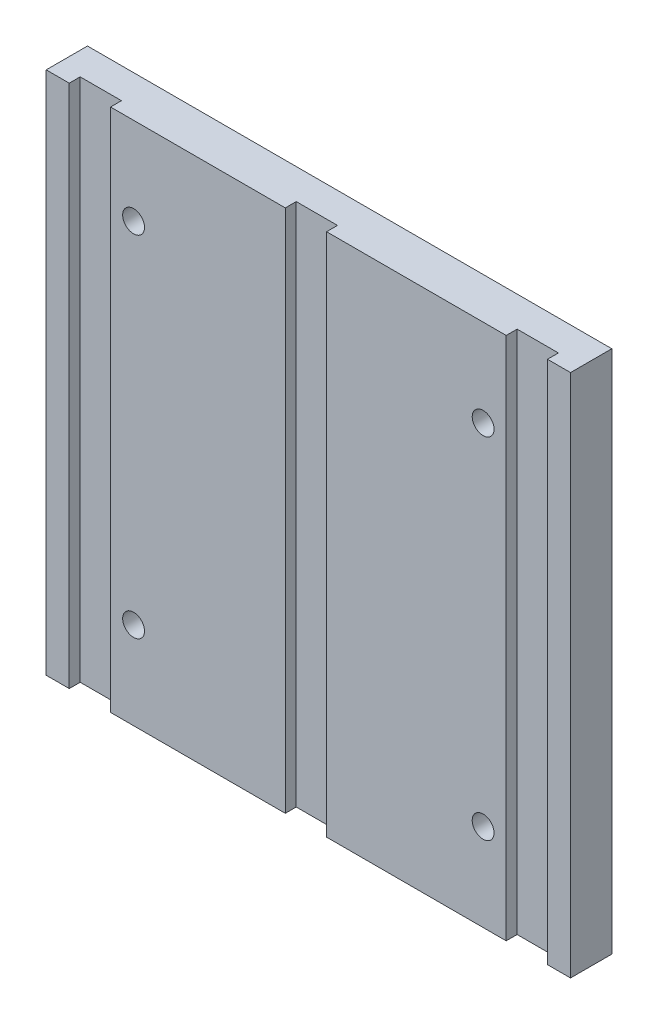
SolidWorks part; units mm, degrees
ref_plane "Front Plane" through (0, 0, 0) normal (0, 0, 1) x (1, 0, 0)
ref_plane "Top Plane" through (0, 0, 0) normal (0, 1, 0) x (1, 0, 0)
ref_plane "Right Plane" through (0, 0, 0) normal (1, 0, 0) x (0, 0, -1)
sketch "Sketch1" plane through (0, 0, 0) normal (0, 0, 1) x (1, 0, 0)
  line L1 (-76.2, 76.2) -> (76.2, 76.2)
  line L2 (-76.2, 76.2) -> (-76.2, -76.2)
  line L3 (-76.2, -76.2) -> (76.2, -76.2)
  line L4 (76.2, 76.2) -> (76.2, -76.2)
  line L5 (-76.2, 76.2) -> (76.2, -76.2) construction
  line L6 (-76.2, -76.2) -> (76.2, 76.2) construction
  circle A0 centre (-50.8, 50.8) radius 3.175
  circle A1 centre (50.8, 50.8) radius 3.175
  circle A2 centre (50.8, -50.8) radius 3.175
  circle A3 centre (-50.8, -50.8) radius 3.175
  point P0 (0, 0)
  dimension "D9" = 6.35
  dimension "D10" = 6.35
  dimension "D13" = 6.35
  dimension "D14" = 6.35
  dimension "D1" = 0
  dimension "D2" = 0
  dimension "D3" = 152.4
  dimension "D4" = 152.4
  dimension "D5" = 25.4
  dimension "D6" = 25.4
  dimension "D7" = 25.4
  dimension "D8" = 25.4
  dimension "D11" = 25.4
  dimension "D12" = 25.4
  dimension "D15" = 25.4
  dimension "D16" = 25.4
extrude "Boss-Extrude1" add sketch "Sketch1" along normal blind 12
sketch "Sketch2" plane through (0, 0, 12) normal (0, 0, 1) x (1, 0, 0)
  line L0 (-76.2, -76.2) -> (76.2, -76.2) construction
  line L1 (-69.5, 76.2) -> (-57.5, 76.2)
  line L2 (-69.5, 76.2) -> (-69.5, -76.2)
  line L3 (-69.5, -76.2) -> (-57.5, -76.2)
  line L4 (-57.5, 76.2) -> (-57.5, -76.2)
  line L5 (-69.5, 76.2) -> (-57.5, -76.2) construction
  line L6 (-69.5, -76.2) -> (-57.5, 76.2) construction
  line L7 (-6.7, 76.2) -> (5.3, 76.2)
  line L8 (-6.7, 76.2) -> (-6.7, -76.2)
  line L9 (-6.7, -76.2) -> (5.3, -76.2)
  line L10 (5.3, 76.2) -> (5.3, -76.2)
  line L11 (-6.7, 76.2) -> (5.3, -76.2) construction
  line L12 (-6.7, -76.2) -> (5.3, 76.2) construction
  line L13 (57.5, 76.2) -> (69.5, 76.2)
  line L14 (57.5, 76.2) -> (57.5, -76.2)
  line L15 (57.5, -76.2) -> (69.5, -76.2)
  line L16 (69.5, 76.2) -> (69.5, -76.2)
  line L17 (57.5, 76.2) -> (69.5, -76.2) construction
  line L18 (57.5, -76.2) -> (69.5, 76.2) construction
  line L19 (-76.2, 76.2) -> (-76.2, -76.2) construction
  line L20 (76.2, -76.2) -> (76.2, 76.2) construction
  point P0 (-63.5, 0)
  point P5 (-0.7, 0)
  point P10 (63.5, 0)
  dimension "D1" = 12
  dimension "D2" = 0
  dimension "D3" = 152.4
  dimension "D4" = 12.7
  dimension "D5" = 0
  dimension "D6" = 12
  dimension "D7" = 152.4
  dimension "D8" = 50.8
  dimension "D9" = 0
  dimension "D10" = 12
  dimension "D11" = 152.4
  dimension "D12" = 12.7
extrude "Cut-Extrude1" cut sketch "Sketch2" against normal blind 3.175
